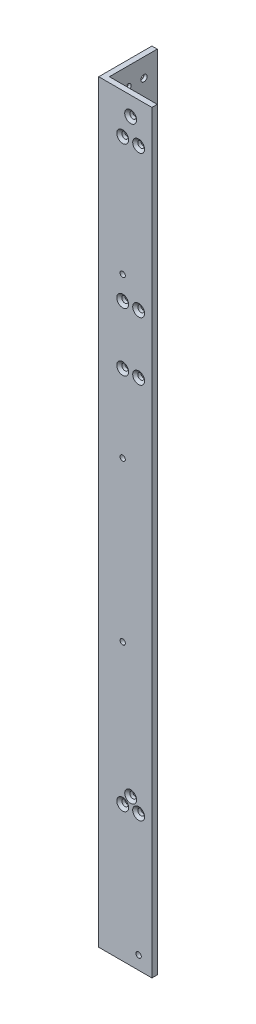
SolidWorks part; units mm, degrees
ref_plane "Front Plane" through (0, 0, 0) normal (0, 0, 1) x (1, 0, 0)
ref_plane "Top Plane" through (0, 0, 0) normal (0, 1, 0) x (1, 0, 0)
ref_plane "Right Plane" through (0, 0, 0) normal (1, 0, 0) x (0, 0, -1)
sketch "Sketch2" plane through (0, 0, 0) normal (0, 1, 0) x (1, 0, 0)
  line L0 (0, 31.75) -> (3.175, 31.75)
  line L1 (3.175, 31.75) -> (3.175, 3.175)
  line L2 (3.175, 3.175) -> (31.75, 3.175)
  line L3 (31.75, 3.175) -> (31.75, 0)
  line L4 (31.75, 0) -> (0, 0)
  line L5 (0, 0) -> (0, 31.75)
  point P9 (1.5875, 31.75)
  point P10 (31.75, 1.5875)
  dimension "D4" = 3.175
  dimension "D1" = 31.75
  dimension "D2" = 31.75
  dimension "D3" = 3.175
extrude "Boss-Extrude1" add sketch "Sketch2" along normal blind 450
sketch "RightSideHoles-Sketch3" plane through (0, 0, 0) normal (0, 0, 1) x (1, 0, 0)
  line L0 (0, 0) -> (31.75, 0) construction
  line L1 (0, 450) -> (31.75, 450) construction
  line L3 (0, 450) -> (0, 0) construction
  circle A0 centre (14.2875, 81.1125) radius 1.5875
  circle A1 centre (23.8125, 81.1125) radius 1.5875
  circle A3 centre (19.05, 87.4625) radius 1.5875
  circle A5 centre (14.2875, 426.1875) radius 1.5875
  circle A6 centre (19.05, 438.8875) radius 1.5875
  circle A7 centre (23.8125, 426.1875) radius 1.5875
  circle A8 centre (14.2875, 341.2474) radius 1.5875
  circle A9 centre (23.8125, 341.2474) radius 1.5875
  circle A10 centre (14.2875, 306.3224) radius 1.5875
  circle A11 centre (23.8125, 306.3224) radius 1.5875
  circle A13 centre (23.8125, 7.9375) radius 1.5875
  circle A14 centre (14.2875, 165) radius 1.5875
  circle A15 centre (14.2875, 260) radius 1.5875
  circle A16 centre (14.2875, 355) radius 1.5875
  point P14 (0, 0)
  point P15 (0, 0)
  dimension "D4" = 3.175
  dimension "D1" = 81.1125
  dimension "D2" = 14.2875
  dimension "D7" = 34.925
  dimension "D10" = 341.2474
  dimension "D11" = 165
  dimension "D13" = 95
  dimension "D5" = 6.35
  dimension "D6" = 12.7
  dimension "D8" = 11.1125
  dimension "D9" = 95
  dimension "D3" = 7.9375
  dimension "D12" = 23.8125
  dimension "D14" = 19.05
sketch "FrontSideHoles-Sketch4" plane through (0, 0, 0) normal (-1, 0, 0) x (0, 0, 1)
  line L0 (-31.75, 450) -> (0, 450) construction
  line L1 (0, 450) -> (0, 0) construction
  line L3 (-31.75, 0) -> (0, 0) construction
  circle A0 centre (-19.05, 81.1125) radius 1.5875
  circle A2 centre (-23.8125, 87.4625) radius 1.5875
  circle A3 centre (-14.2875, 87.4625) radius 1.5875
  circle A4 centre (-23.8125, 438.8875) radius 1.5875
  circle A5 centre (-14.2875, 438.8875) radius 1.5875
  circle A6 centre (-19.05, 426.1875) radius 1.5875
  circle A8 centre (-14.2875, 354.1849) radius 2
  circle A9 centre (-14.2875, 313.9849) radius 2
  circle A10 centre (-14.2875, 165) radius 1.5875
  circle A11 centre (-14.2875, 260) radius 1.5875
  circle A13 centre (-23.8125, 7.9375) radius 1.5875
  dimension "D4" = 3.175
  dimension "D13" = 95
  dimension "D5" = 6.35
  dimension "D16" = 4
  dimension "D6" = 11.1125
  dimension "D9" = 40.2
  dimension "D10" = 14.2875
  dimension "D7" = 12.7
  dimension "D12" = 165
  dimension "D15" = 7.9375
  dimension "D2" = 14.2875
  dimension "D3" = 81.1125
  dimension "D8" = 354.1849
  dimension "D14" = 19.05
  dimension "D11" = 23.8125
extrude "RightSideHoles-Cut-Extrude1" cut sketch "RightSideHoles-Sketch3" against normal blind 3.175
extrude "FrontSideHoles-Cut-Extrude2" cut sketch "FrontSideHoles-Sketch4" against normal blind 3.175
sketch "Sketch5" plane through (0, 0, 0) normal (-1, 0, 0) x (0, 0, 1)
  point P0 (-23.8125, 438.8875)
  point P3 (-19.05, 426.1875)
  point P6 (-14.2875, 438.8875)
  point P9 (-19.05, 81.1125)
  point P12 (-14.2875, 87.4625)
  point P15 (-23.8125, 87.4625)
hole_wizard "CSK for #6 Flat Head Machine Screw (100)2" positions "Sketch5" profile "Sketch6" countersink size "#6" standard "ANSI Inch" end condition through all
sketch "Sketch6" plane through (0, 438.8875, -23.8125) normal (0, 1, 0) x (0, 0, 1)
  line L0 (0, 0) -> (0, 31.75)
  line L1 (0, 31.75) -> (1.8986, 31.75)
  line L2 (1.8986, 31.75) -> (1.8986, 1.38)
  line L3 (1.8986, 1.38) -> (3.5433, 0)
  line L5 (3.5433, 0) -> (0, 0)
  line L6 (-1.8986, 1.38) -> (-3.5433, 0) construction
  line L11 (0, -6.35) -> (0, 107.95) construction
  dimension "Thru Hole Dia." = 3.7973
  dimension "Thru Hole Depth" = 31.75
  dimension "Near C'Sink Dia." = 7.0866
  dimension "Near C'Sink Angle" = 100
sketch "Sketch11" plane through (0, 0, 0) normal (0, 0, 1) x (1, 0, 0)
  point P0 (14.2875, 81.1125)
  point P3 (19.05, 87.4625)
  point P6 (23.8125, 81.1125)
  point P9 (14.2875, 306.3224)
  point P12 (23.8125, 306.3224)
  point P15 (14.2875, 341.2474)
  point P18 (23.8125, 341.2474)
  point P21 (14.2875, 426.1875)
  point P24 (23.8125, 426.1875)
  point P27 (19.05, 438.8875)
hole_wizard "CSK for #6 Flat Head Machine Screw (100)3" positions "Sketch11" profile "Sketch12" countersink size "#6" standard "ANSI Inch" end condition through all
sketch "Sketch12" plane through (14.2875, 81.1125, 0) normal (1, 0, 0) x (0, -1, 0)
  line L0 (0, 0) -> (0, 31.75)
  line L1 (0, 31.75) -> (1.8986, 31.75)
  line L2 (1.8986, 31.75) -> (1.8986, 1.38)
  line L3 (1.8986, 1.38) -> (3.5433, 0)
  line L5 (3.5433, 0) -> (0, 0)
  line L6 (-1.8986, 1.38) -> (-3.5433, 0) construction
  line L11 (0, -6.35) -> (0, 107.95) construction
  dimension "Thru Hole Dia." = 3.7973
  dimension "Thru Hole Depth" = 31.75
  dimension "Near C'Sink Dia." = 7.0866
  dimension "Near C'Sink Angle" = 100
equation "\"RailThickness\"= .125in'Spec"
equation "\"VSWidth\"= 1.25in'Spec"
equation "\"VSHeight\"= 1.25in'Spec"
equation "\"VSLength\"= 450mm"
equation "\"HoleOffsetFromEdge\"= \"RailThickness\" * 2.5"
equation "\"HoleOffsetFromSide\"= \"RailThickness\" * 3.5"
equation "\"LegHeight\"= 70mm'Space needed for PSU/Stepper/Electronics"
equation "\"VSBottomSideRailHoleY1FromBottomOfLowerRail\"= \"V1 BottomOfLowerRail\" + \"HoleOffsetFromSide\"'Equals 81.1125"
equation "\"VSSideRailHoleX1FromSide\"= \"HoleOffsetFromSide\" + \"RailThickness\""
equation "\"FasteningHoleDiameter\"= .125in"
equation "\"VSBottomSideRailHoleY2FromY1\"= \"LowerRailHeight\" - \"HoleOffsetFromSide\" - \"HoleOffsetFromEdge\"'Equals 6.35"
equation "\"VSTopSideRailHoleY1FromEdge\"= \"HoleOffsetFromEdge\" + \"RailThickness\""
equation "\"D4@RightSideHoles-Sketch3\" = \"FasteningHoleDiameter\""
equation "\"D1@RightSideHoles-Sketch3\" = \"VSBottomSideRailHoleY1FromBottomOfLowerRail\""
equation "\"D2@RightSideHoles-Sketch3\" = \"VSSideRailHoleX1FromSide\""
equation "\"D1@Boss-Extrude1\"=\"VSLength\""
equation "\"D4@FrontSideHoles-Sketch4\" = \"FasteningHoleDiameter\""
equation "\"D6@FrontSideHoles-Sketch4\" = \"VSTopSideRailHoleY1FromEdge\""
equation "\"VSMidSideRailHoleY1FromV8TopOfMidSideRail\"= \"V8 ToTopOfMidSideRail\" - \"HoleOffsetFromEdge\"'Equals 341.24737"
equation "\"LowerRailHeight\"= 1.00in"
equation "\"D2@Sketch2\"=\"VSWidth\""
equation "\"D1@Sketch2\"=\"VSHeight\""
equation "\"TopRailHeight\"= 1.25in"
equation "\"MidLeftOrRightSideRailHeight\"= 2.0in"
equation "\"VSMidSideRailHoleY2FromY1\"= \"MidLeftOrRightSideRailHeight\" - \"HoleOffsetFromEdge\" * 2'Equals 34.925"
equation "\"D7@RightSideHoles-Sketch3\"=\"VSMidSideRailHoleY2FromY1\""
equation "\"VSTopSideRailHoleY2FromY1\"= \"TopRailHeight\" - \"VSTopSideRailHoleY1FromEdge\" - \"HoleOffsetFromEdge\"'Equals 12.7"
equation "\"D7@FrontSideHoles-Sketch4\"=\"VSTopSideRailHoleY2FromY1\""
equation "\"VSSideRailHoleX2FromSide\"= \"VSWidth\" - \"HoleOffsetFromEdge\""
equation "\"1mmSpacer\"= 1mm"
equation "\"20TGT2PulleyWidth\"= 8.7mm'The STL of the Pulley in the diagram is a bit larger"
equation "\"BeltTensionerInnerHeight\"= \"20TGT2PulleyWidth\" * 2 + \"1mmSpacer\" * 3"
equation "\"BeltTensionerHeight\"= 60mm"
equation "\"D9@FrontSideHoles-Sketch4\"=\"VSBeltTensionerHoleY2FromY1\""
equation "\"VSBeltTensionerHoleY1ToAlignedWithYAxisGantryBlockUpperPulley\"= \"V5 ToBottomOfXAxisLinearRail\" - \"DistanceFromXAxisLinearRailBottomAndTopGantryPulley\" + \"DistanceFromBeltTensionerTopPulleyToBeltTensionerTop\" - \"BeltTensionerMountingHoleOffsetFromTopOrBottom\"'Equals 354.18487"
equation "\"VSBeltTensionerHoleY2FromY1\"= \"BeltTensionerHeight\" - \"BeltTensionerMountingHoleOffsetFromTopOrBottom\" * 2"
equation "\"V1 BottomOfLowerRail\"= \"LegHeight\""
equation "\"StepperShaftLength\"= 24mm'Pulley will be attached to the end"
equation "\"ZAxisLeadScrewLength\"= 200mm"
equation "\"LM8UUHeight\"= 24mm'Spec"
equation "\"V2 ToBedAtTopOfZAxis\"= \"V1 BottomOfLowerRail\" - \"LowerEnclosureThickness\" + \"StepperShaftLength\" + \"ZAxisLeadScrewLength\" - \"LM8UUHeight\" / 2'Equals 277"
equation "\"HotEndToTopOfXAxisGB\"= 71.68487mm'Equals 71.68487. Measured after installed onto X-Axis linear rail guide block"
equation "\"TopOfGBToBottomOfLinearRail\"= \"LinearGBWidth\" / 2 + \"LinearRailWidth\" / 2'Equals 19.5"
equation "\"LinearGBWidth\"= 27mm'Spec"
equation "\"V5 ToBottomOfXAxisLinearRail\"= \"V4 ToTopOfBuildPlate/HotEndTip\" + \"HotEndToTopOfXAxisGB\" - \"TopOfGBToBottomOfLinearRail\"'Equals 352.18487"
equation "\"LinearRailWidth\"= 12mm'Spec"
equation "\"V6 ToMiddleOfYAxisGantryBlock\"= \"V5 ToBottomOfXAxisLinearRail\" - \"GABHeight\" / 2'Equals 334.18487"
equation "\"GABUpperHeight\"= 4mm"
equation "\"GABMidWallHeight\"= 28mm'Must equal 28 or changes alignment"
equation "\"D10@RightSideHoles-Sketch3\"=\"VSMidSideRailHoleY1FromV8TopOfMidSideRail\""
equation "\"BedToBuildPlateStandoffLength\"= 15mm"
equation "\"BuildPlateHeight\"= 8mm'Spec"
equation "\"V4 ToTopOfBuildPlate/HotEndTip\"= \"V2 ToBedAtTopOfZAxis\" + \"BedToBuildPlateStandoffLength\" + \"BuildPlateHeight\""
equation "\"V8 ToTopOfMidSideRail\"= \"V6 ToMiddleOfYAxisGantryBlock\" + \"MidSideRailVerticalOffset\"'Equals 349.18487"
equation "\"BeltTensionerMountingHoleOffsetFromEdge\"= \"HoleOffsetFromEdge\""
equation "\"VSBeltTensionerXMountingHoleOffsetFromSide\"= \"BeltTensionerMountingHoleOffsetFromEdge\" + \"RailThickness\" * 2"
equation "\"D10@FrontSideHoles-Sketch4\"=\"VSBeltTensionerXMountingHoleOffsetFromSide\""
equation "\"VSEnclosureOffsets\"= ( \"VSLength\" - \"LegHeight\" ) / 4"
equation "\"D11@RightSideHoles-Sketch3\"=\"LegHeight\" + \"VSEnclosureOffsets\""
equation "\"D13@RightSideHoles-Sketch3\"=\"VSEnclosureOffsets\""
equation "\"D12@FrontSideHoles-Sketch4\"= \"LegHeight\" + \"VSEnclosureOffsets\""
equation "\"D13@FrontSideHoles-Sketch4\"=\"VSEnclosureOffsets\""
equation "\"D15@FrontSideHoles-Sketch4\"=\"HoleOffsetFromEdge\""
equation "\"D2@FrontSideHoles-Sketch4\"=\"VSSideRailHoleX1FromSide\""
equation "\"D5@FrontSideHoles-Sketch4\"=\"VSBottomSideRailHoleY2FromY1\""
equation "\"D3@FrontSideHoles-Sketch4\"=\"VSBottomSideRailHoleY1FromBottomOfLowerRail\""
equation "\"D5@RightSideHoles-Sketch3\"=\"VSBottomSideRailHoleY2FromY1\""
equation "\"D6@RightSideHoles-Sketch3\"=\"VSTopSideRailHoleY2FromY1\""
equation "\"D8@RightSideHoles-Sketch3\"=\"VSTopSideRailHoleY1FromEdge\""
equation "\"BeltTensionerMountingHoleDiameter\"= 4.0mm"
equation "\"D16@FrontSideHoles-Sketch4\"=\"BeltTensionerMountingHoleDiameter\""
equation "\"LowerEnclosureThickness\"= 5mm"
equation "\"GABLowerHeight\"= 4mm"
equation "\"GABHeight\"= \"GABLowerHeight\" + \"GABMidWallHeight\" + \"GABUpperHeight\""
equation "\"D9@RightSideHoles-Sketch3\"=\"VSEnclosureOffsets\""
equation "\"BeltTensionerMountingHoleOffsetFromTopOrBottom\"= ( \"BeltTensionerHeight\" - \"BeltTensionerInnerHeight\" ) / 4"
equation "\"MidSideRailVerticalOffset\"= \"LinearRailWidth\" + 3mm'Allows space for RodStabilizer to attach to bottom of MidSideRail"
equation "\"GABRiserBossOffset\"= 0.4mm'Aligns Pulleys inside edges to be 2.5mm (.5mm apart top to bottom)"
equation "\"GABMidShortRiserHeight\"= \"GABMidWallHeight\" / 2 - \"20TGT2PulleyWidth\"'Equals 5.3"
equation "\"7mmx1mmSpacerHeight\"= 1mm"
equation "\"D8@FrontSideHoles-Sketch4\"=\"VSBeltTensionerHoleY1ToAlignedWithYAxisGantryBlockUpperPulley\""
equation "\"DistanceFromXAxisLinearRailBottomAndTopGantryPulley\"= \"GABUpperHeight\" + \"GABMidShortRiserHeight\" - \"GABRiserBossOffset\"'Equals 8.9"
equation "\"DistanceFromBeltTensionerTopPulleyToBeltTensionerTop\"= \"7mmx1mmSpacerHeight\" + \"BeltTensionerTopHeight\"'Equals 20.8"
equation "\"BeltTensionerTopHeight\"= ( \"BeltTensionerHeight\" - \"BeltTensionerInnerHeight\" ) / 2'Equals 19.8"
equation "\"VSMidSideRailHoleXFromSideToCenter\"= \"RailThickness\" * 6"
equation "\"D14@FrontSideHoles-Sketch4\"=\"VSMidSideRailHoleXFromSideToCenter\""
equation "\"D3@RightSideHoles-Sketch3\"=\"HoleOffsetFromEdge\""
equation "\"D14@RightSideHoles-Sketch3\"=\"VSMidSideRailHoleXFromSideToCenter\""
equation "\"D12@RightSideHoles-Sketch3\"=\"VSSideRailHoleX2FromSide\""
equation "\"D11@FrontSideHoles-Sketch4\"=\"VSSideRailHoleX2FromSide\""
